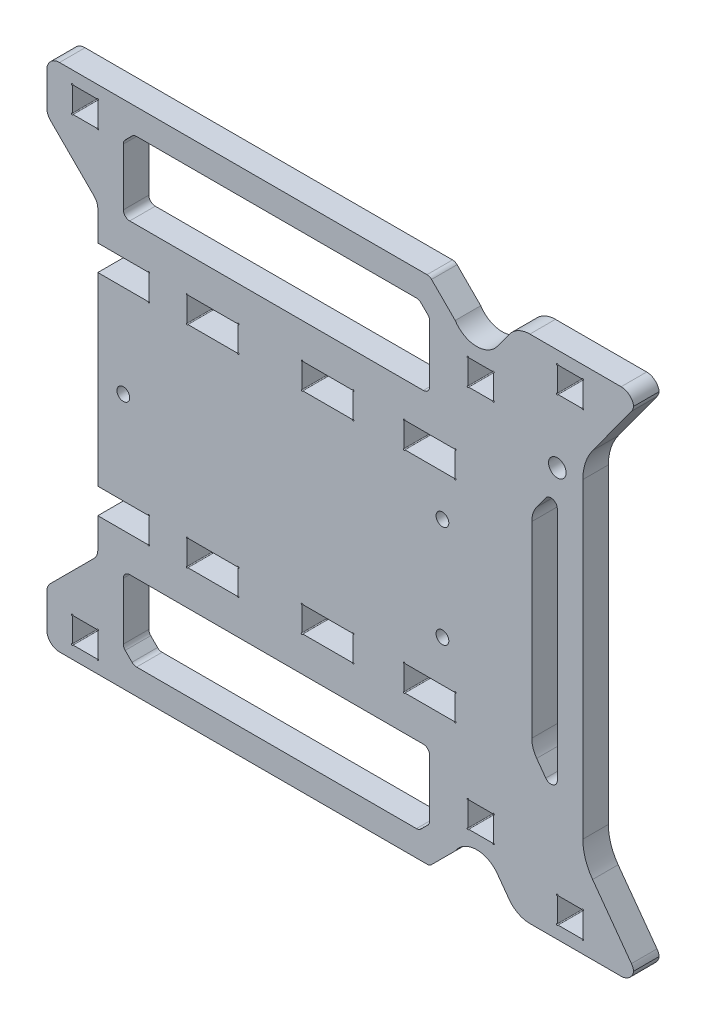
SolidWorks part; units mm, degrees
ref_plane "Front Plane" through (0, 0, 0) normal (0, 0, 1) x (1, 0, 0)
ref_plane "Top Plane" through (0, 0, 0) normal (0, 1, 0) x (1, 0, 0)
ref_plane "Right Plane" through (0, 0, 0) normal (1, 0, 0) x (0, 0, -1)
sketch "Sketch1" plane through (0, 0, 0) normal (0, 0, 1) x (1, 0, 0)
  line L0 (83.672, 0) -> (-43.8164, 0) construction
  line L1 (10.525, 38.1) -> (10.525, -38.1) construction
  line L2 (-27.575, 38.1) -> (48.625, 38.1)
  line L3 (99.425, -63.5) -> (99.425, -60.325)
  line L4 (99.425, -60.325) -> (74.025, -25.4)
  line L5 (-27.575, -63.5) -> (48.625, -63.5)
  line L6 (-27.575, 38.1) -> (-27.575, 54.5197)
  line L7 (48.625, 38.1) -> (48.625, 54.5197)
  line L8 (-24.9447, 57.15) -> (45.9947, 57.15)
  line L9 (-27.575, 63.5) -> (48.625, 63.5)
  line L10 (-33.925, 57.15) -> (-33.925, -57.15)
  line L11 (-27.575, 63.5) -> (-33.925, 57.15)
  line L12 (-24.9447, 57.15) -> (-27.575, 54.5197)
  line L13 (99.425, 63.5) -> (99.425, 60.325)
  line L14 (-23.0849, 59.0099) -> (-29.4349, 52.6599) construction
  line L15 (99.425, 60.325) -> (74.025, 25.4)
  line L16 (74.025, 25.4) -> (74.025, -25.4)
  line L17 (48.625, -38.1) -> (48.625, -54.5197)
  line L18 (-27.575, -38.1) -> (48.625, -38.1)
  line L19 (-24.9447, -57.15) -> (45.9947, -57.15)
  line L20 (-24.9447, -57.15) -> (-27.575, -54.5197)
  line L21 (-27.575, -38.1) -> (-27.575, -54.5197)
  line L22 (-27.575, -63.5) -> (-33.925, -57.15)
  line L23 (48.625, -63.5) -> (54.975, -57.15)
  line L24 (48.625, 63.5) -> (54.975, 57.15)
  line L25 (70.3271, -63.5) -> (99.425, -63.5)
  line L26 (45.9947, 57.15) -> (48.625, 54.5197)
  line L27 (45.9947, -57.15) -> (48.625, -54.5197)
  line L28 (70.3271, 63.5) -> (65.7089, 57.15)
  line L29 (70.3271, 63.5) -> (99.425, 63.5)
  line L30 (78.8831, 75.2646) -> (53.4831, 40.3396) construction
  line L31 (54.975, -42.3909) -> (54.975, -57.15)
  line L32 (70.3271, -63.5) -> (65.7089, -57.15)
  line L34 (48.625, -63.5) -> (54.975, -57.15)
  line L35 (65.7089, 57.15) -> (54.975, 42.3909)
  line L36 (54.975, 42.3909) -> (54.975, 57.15)
  line L37 (65.7089, -57.15) -> (54.975, -42.3909)
  point P7 (-27.575, 0)
  point P21 (74.025, 0)
  point P22 (-33.925, 0)
  dimension "D1" = 25.4
  dimension "D2" = 76.2
  dimension "D3" = 127
  dimension "D4" = 6.35
  dimension "D7" = 3.175
  dimension "D8" = 25.4
  dimension "D9" = 25.4
  dimension "D6" = 6.35
extrude "Boss-Extrude1" add sketch "Sketch1" along normal blind 6.35 contours L23 L32 L25 L3 L4 L16 L15 L13 L29 L28 L24 L9 L11 L10 L22 L5 L8 L26 L7 L2 L6 L12 L27 L19 L20 L21 L18 L17 region at (27.1557, 0, 0)
fillet "Fillet1" radius 6.35 4 edges at (70.3271, 63.5, 3.175) (70.3271, -63.5, 3.175) (54.975, -42.3909, 3.175) (54.975, 42.3909, 3.175)
fillet "Fillet3" radius 3.175 4 edges at (99.425, 63.5, 3.175) (99.425, 60.325, 3.175) (99.425, -60.325, 3.175) (99.425, -63.5, 3.175)
fillet "Fillet4" radius 6.35 2 edges at (74.025, -25.4, 3.175) (74.025, 25.4, 3.175)
fillet "Fillet7" radius 1.5875 4 edges at (-27.575, -38.1, 3.175) (48.625, -38.1, 3.175) (48.625, 38.1, 3.175) (-27.575, 38.1, 3.175)
fillet "Fillet8" radius 1.5875 2 edges at (48.625, -63.5, 3.175) (48.625, 63.5, 3.175)
fillet "Fillet9" radius 1.5875 8 edges at (-27.575, 54.5197, 3.175) (-24.9447, 57.15, 3.175) (-27.575, -54.5197, 3.175) (-24.9447, -57.15, 3.175) (45.9947, -57.15, 3.175) (48.625, -54.5197, 3.175) (48.625, 54.5197, 3.175) (45.9947, 57.15, 3.175)
sketch "Sketch2" plane through (0, 0, 6.35) normal (0, 0, 1) x (1, 0, 0)
  line L0 (-33.925, 0) -> (74.025, 0) construction
  line L1 (-33.925, 57.15) -> (-33.925, -57.15) construction
  line L2 (74.025, 23.3351) -> (74.025, -23.3351) construction
  line L3 (48.625, 39.6875) -> (48.625, 53.8622) construction
  line L4 (58.3484, 50.8) -> (64.3016, 50.8)
  line L5 (58.15, 50.6016) -> (58.15, 44.6484)
  line L6 (58.3484, 44.45) -> (64.3016, 44.45)
  line L7 (64.5, 50.6016) -> (64.5, 44.6484)
  line L8 (64.5, -50.6016) -> (64.5, -44.6484)
  line L9 (58.3484, -50.8) -> (64.3016, -50.8)
  line L10 (58.15, -50.6016) -> (58.15, -44.6484)
  line L11 (58.3484, -44.45) -> (64.3016, -44.45)
  arc A0 (58.3484, 50.8) -> (58.15, 50.6016) centre (58.15, 50.8) ccw
  arc A1 (64.5, 50.6016) -> (64.3016, 50.8) centre (64.5, 50.8) ccw
  arc A2 (64.3016, 44.45) -> (64.5, 44.6484) centre (64.5, 44.45) ccw
  arc A3 (58.15, 44.6484) -> (58.3484, 44.45) centre (58.15, 44.45) ccw
  arc A4 (64.3016, -44.45) -> (64.5, -44.6484) centre (64.5, -44.45) cw
  arc A5 (64.5, -50.6016) -> (64.3016, -50.8) centre (64.5, -50.8) cw
  arc A6 (58.3484, -50.8) -> (58.15, -50.6016) centre (58.15, -50.8) cw
  arc A7 (58.15, -44.6484) -> (58.3484, -44.45) centre (58.15, -44.45) cw
  point P10 (48.625, 46.7748)
  dimension "D5" = 0.3969
  dimension "D6" = 0.3969
  dimension "D7" = 0.3969
  dimension "D8" = 0.3969
  dimension "D1" = 6.35
  dimension "D2" = 6.35
  dimension "D3" = 50.8
  dimension "D4" = 9.525
extrude "Cut-Extrude1" cut sketch "Sketch2" against normal through all
sketch "Sketch5" plane through (0, 0, 6.35) normal (0, 0, 1) x (1, 0, 0)
  line L0 (-33.925, 29.3675) -> (74.025, 29.3675) construction
  line L1 (-33.925, 57.15) -> (-33.925, -57.15) construction
  line L2 (74.025, 23.3351) -> (74.025, -23.3351) construction
  line L3 (-25.9875, 38.1) -> (47.0375, 38.1) construction
  line L4 (-33.925, 23.0175) -> (74.025, 23.0175) construction
  line L5 (-33.925, 0) -> (74.025, 0) construction
  line L6 (-11.5016, 29.3675) -> (0.8016, 29.3675)
  line L7 (-11.7, 29.169) -> (-11.7, 23.2159)
  line L8 (-11.5016, 23.0175) -> (0.8016, 23.0175)
  line L9 (1, 29.169) -> (1, 23.2159)
  line L10 (42.4734, 29.3675) -> (54.7766, 29.3675)
  line L11 (42.275, 29.169) -> (42.275, 23.2159)
  line L12 (42.4734, 23.0175) -> (54.7766, 23.0175)
  line L13 (54.975, 29.169) -> (54.975, 23.2159)
  line L14 (29.3766, 29.3675) -> (17.0734, 29.3675)
  line L15 (29.575, 29.169) -> (29.575, 23.2159)
  line L16 (29.3766, 23.0175) -> (17.0734, 23.0175)
  line L17 (16.875, 29.169) -> (16.875, 23.2159)
  line L18 (-21.4234, 29.3675) -> (-33.925, 29.3675)
  line L19 (-21.225, 29.169) -> (-21.225, 23.2159)
  line L20 (-21.4234, 23.0175) -> (-33.925, 23.0175)
  line L21 (-33.925, 29.3675) -> (-33.925, 23.0175)
  line L22 (-33.925, -29.3675) -> (-33.925, -23.0175)
  line L23 (-21.4234, -23.0175) -> (-33.925, -23.0175)
  line L24 (-21.225, -29.169) -> (-21.225, -23.2159)
  line L25 (-21.4234, -29.3675) -> (-33.925, -29.3675)
  line L26 (16.875, -29.169) -> (16.875, -23.2159)
  line L27 (29.3766, -23.0175) -> (17.0734, -23.0175)
  line L28 (29.575, -29.169) -> (29.575, -23.2159)
  line L29 (29.3766, -29.3675) -> (17.0734, -29.3675)
  line L30 (54.975, -29.169) -> (54.975, -23.2159)
  line L31 (42.4734, -23.0175) -> (54.7766, -23.0175)
  line L32 (42.275, -29.169) -> (42.275, -23.2159)
  line L33 (42.4734, -29.3675) -> (54.7766, -29.3675)
  line L34 (1, -29.169) -> (1, -23.2159)
  line L35 (-11.5016, -23.0175) -> (0.8016, -23.0175)
  line L36 (-11.7, -29.169) -> (-11.7, -23.2159)
  line L37 (-11.5016, -29.3675) -> (0.8016, -29.3675)
  line L38 (-33.925, 26.1925) -> (54.975, 26.1925) construction
  arc A0 (-21.225, 29.169) -> (-21.4234, 29.3675) centre (-21.225, 29.3675) ccw
  arc A1 (-11.5016, 29.3675) -> (-11.7, 29.169) centre (-11.7, 29.3675) ccw
  arc A2 (1, 29.169) -> (0.8016, 29.3675) centre (1, 29.3675) ccw
  arc A3 (29.575, 29.169) -> (29.3766, 29.3675) centre (29.575, 29.3675) ccw
  arc A4 (17.0734, 29.3675) -> (16.875, 29.169) centre (16.875, 29.3675) ccw
  arc A5 (54.975, 29.169) -> (54.7766, 29.3675) centre (54.975, 29.3675) ccw
  arc A6 (42.4734, 29.3675) -> (42.275, 29.169) centre (42.275, 29.3675) ccw
  arc A7 (17.0734, 23.0175) -> (16.875, 23.2159) centre (16.875, 23.0175) cw
  arc A8 (29.575, 23.2159) -> (29.3766, 23.0175) centre (29.575, 23.0175) cw
  arc A9 (42.4734, 23.0175) -> (42.275, 23.2159) centre (42.275, 23.0175) cw
  arc A10 (54.975, 23.2159) -> (54.7766, 23.0175) centre (54.975, 23.0175) cw
  arc A11 (1, 23.2159) -> (0.8016, 23.0175) centre (1, 23.0175) cw
  arc A12 (-11.5016, 23.0175) -> (-11.7, 23.2159) centre (-11.7, 23.0175) cw
  arc A13 (-21.225, 23.2159) -> (-21.4234, 23.0175) centre (-21.225, 23.0175) cw
  arc A14 (-21.225, -23.2159) -> (-21.4234, -23.0175) centre (-21.225, -23.0175) ccw
  arc A15 (-11.5016, -23.0175) -> (-11.7, -23.2159) centre (-11.7, -23.0175) ccw
  arc A16 (1, -23.2159) -> (0.8016, -23.0175) centre (1, -23.0175) ccw
  arc A17 (54.975, -23.2159) -> (54.7766, -23.0175) centre (54.975, -23.0175) ccw
  arc A18 (42.4734, -23.0175) -> (42.275, -23.2159) centre (42.275, -23.0175) ccw
  arc A19 (29.575, -23.2159) -> (29.3766, -23.0175) centre (29.575, -23.0175) ccw
  arc A20 (17.0734, -23.0175) -> (16.875, -23.2159) centre (16.875, -23.0175) ccw
  arc A21 (42.4734, -29.3675) -> (42.275, -29.169) centre (42.275, -29.3675) cw
  arc A22 (54.975, -29.169) -> (54.7766, -29.3675) centre (54.975, -29.3675) cw
  arc A23 (17.0734, -29.3675) -> (16.875, -29.169) centre (16.875, -29.3675) cw
  arc A24 (29.575, -29.169) -> (29.3766, -29.3675) centre (29.575, -29.3675) cw
  arc A25 (1, -29.169) -> (0.8016, -29.3675) centre (1, -29.3675) cw
  arc A26 (-11.5016, -29.3675) -> (-11.7, -29.169) centre (-11.7, -29.3675) cw
  arc A27 (-21.225, -29.169) -> (-21.4234, -29.3675) centre (-21.225, -29.3675) cw
  dimension "D11" = 0.3969
  dimension "D12" = 0.3969
  dimension "D13" = 0.3969
  dimension "D14" = 0.3969
  dimension "D15" = 0.3969
  dimension "D16" = 0.3969
  dimension "D17" = 0.3969
  dimension "D1" = 8.7325
  dimension "D3" = 12.7
  dimension "D4" = 12.7
  dimension "D5" = 41.275
  dimension "D6" = 34.925
  dimension "D7" = 12.7
  dimension "D8" = 12.7
  dimension "D9" = 50.8
  dimension "D10" = 0
  dimension "D2" = 6.35
extrude "Cut-Extrude4" cut sketch "Sketch5" against normal through all
sketch "Sketch6" plane through (0, 0, 6.35) normal (0, 0, 1) x (1, 0, 0)
  line L0 (80.375, 34.1312) -> (80.375, -34.1312)
  line L1 (98.8177, 59.49) -> (75.2395, 27.07) construction
  line L2 (98.8177, -59.49) -> (75.2395, -27.07) construction
  line L3 (74.025, 23.3351) -> (74.025, -23.3351) construction
  line L4 (86.725, 34.1312) -> (86.725, -34.1312)
  line L5 (86.725, 34.1312) -> (86.725, 42.8625)
  line L6 (86.725, 42.8625) -> (80.375, 34.1312)
  line L7 (86.725, -34.1312) -> (86.725, -42.8625)
  line L8 (86.725, -42.8625) -> (80.375, -34.1312)
  dimension "D1" = 6.35
  dimension "D2" = 6.35
extrude "Boss-Extrude2" add sketch "Sketch6" against normal blind 6.35
fillet "Fillet10" radius 1.5875 2 edges at (80.375, -34.1312, 3.175) (80.375, 34.1312, 3.175)
fillet "Fillet11" radius 12.7 2 edges at (86.725, 42.8625, 3.175) (86.725, -42.8625, 3.175)
hole_wizard "11/64 (0.17188) Diameter Hole1" positions "Sketch8" profile "Sketch7" hole size "11/64" standard "ANSI Inch" end condition through all
sketch "Sketch8" plane through (0, 0, 6.35) normal (0, 0, 1) x (1, 0, 0)
  line L1 (-33.925, -29.3675) -> (-33.925, -57.15) construction
  line L2 (73.5606, 63.5) -> (96.25, 63.5) construction
  point P0 (80.375, 38.1)
  dimension "D1" = 25.4
  dimension "D2" = 114.3
sketch "Sketch7" plane through (80.375, 38.1, 6.35) normal (1, 0, 0) x (0, -1, 0)
  line L0 (0, 0) -> (0, 6.35)
  line L1 (0, 6.35) -> (2.1829, 6.35)
  line L2 (2.1829, 6.35) -> (2.1829, 0)
  line L5 (2.1829, 0) -> (0, 0)
  line L11 (0, -6.35) -> (0, 107.95) construction
  dimension "Thru Hole Dia." = 4.3658
  dimension "Thru Hole Depth" = 6.35
sketch "Sketch10" plane through (0, 0, 6.35) normal (0, 0, 1) x (1, 0, 0)
  line L0 (51.8, 63.5) -> (51.8, -63.5) construction
  line L1 (-27.575, 63.5) -> (47.9674, 63.5) construction
  line L2 (-27.575, -63.5) -> (47.9674, -63.5) construction
  line L3 (23.225, 29.3675) -> (23.225, -29.3675) construction
  line L4 (29.3766, 29.3675) -> (17.0734, 29.3675) construction
  line L5 (17.0734, -29.3675) -> (29.3766, -29.3675) construction
  line L6 (-27.575, 63.5) -> (-27.575, -63.5) construction
  line L7 (-33.925, 0) -> (74.025, 0) construction
  line L8 (-33.925, 23.0175) -> (-33.925, -23.0175) construction
  line L9 (74.025, 23.3351) -> (74.025, -23.3351) construction
  circle A0 centre (51.8, 12.7) radius 1.5875
  circle A1 centre (51.8, -12.7) radius 1.5875
  circle A2 centre (-27.575, 0) radius 1.5875
  dimension "D3" = 3.175
  dimension "D5" = 79.375
  dimension "D1" = 28.575
  dimension "D2" = 79.375
  dimension "D4" = 12.7
extrude "Cut-Extrude6" cut sketch "Sketch10" against normal through all
sketch "Sketch11" plane through (0, 0, 6.35) normal (0, 0, 1) x (1, 0, 0)
  line L0 (-62.0481, -60.325) -> (124.8486, -60.325) construction
  line L1 (-27.575, -63.5) -> (47.9674, -63.5) construction
  line L2 (-27.575, -63.5) -> (-33.925, -57.15)
  line L3 (-33.925, -57.15) -> (-33.925, -50.8)
  line L4 (-33.925, -50.8) -> (-33.925, -38.1)
  line L5 (-46.625, -50.8) -> (-46.625, -63.5)
  line L6 (-46.625, -63.5) -> (-27.575, -63.5)
  line L7 (-46.625, -50.8) -> (-33.925, -38.1)
  line L8 (-33.925, -29.3675) -> (-33.925, -57.15) construction
  line L9 (-46.625, 63.5) -> (-27.575, 63.5)
  line L10 (-33.925, 0) -> (74.025, 0) construction
  line L11 (-46.625, 50.8) -> (-46.625, 63.5)
  line L12 (-33.925, 23.0175) -> (-33.925, -23.0175) construction
  line L13 (74.025, 23.3351) -> (74.025, -23.3351) construction
  line L14 (-46.625, 50.8) -> (-33.925, 38.1)
  line L15 (-33.925, 57.15) -> (-33.925, 50.8)
  line L16 (-27.575, 63.5) -> (-33.925, 57.15)
  line L17 (-33.925, 50.8) -> (-33.925, 38.1)
  point P2 (10.1962, -63.5)
  dimension "D1" = 3.175
  dimension "D2" = 12.7
  dimension "D3" = 12.7
extrude "Boss-Extrude4" add sketch "Sketch11" against normal blind 6.35
sketch "Sketch12" plane through (0, 0, 6.35) normal (0, 0, 1) x (1, 0, 0)
  line L0 (73.5606, -63.5) -> (96.25, -63.5) construction
  line L1 (86.5266, -60.325) -> (80.5734, -60.325)
  line L2 (86.725, -60.1266) -> (86.725, -54.1734)
  line L3 (86.5266, -53.975) -> (80.5734, -53.975)
  line L4 (80.375, -60.1266) -> (80.375, -54.1734)
  line L5 (-33.925, -29.3675) -> (-33.925, -38.1) construction
  line L6 (-33.925, 0) -> (74.025, 0) construction
  line L7 (86.725, 60.1266) -> (86.725, 54.1734)
  line L8 (86.5266, 60.325) -> (80.5734, 60.325)
  line L9 (80.375, 60.1266) -> (80.375, 54.1734)
  line L10 (86.5266, 53.975) -> (80.5734, 53.975)
  line L11 (83.55, -60.325) -> (-33.7266, -60.325) construction
  line L12 (-34.1234, -60.325) -> (-54.5439, -60.325) construction
  line L13 (-34.1234, -60.325) -> (-40.0766, -60.325)
  line L14 (-33.925, -60.1266) -> (-33.925, -54.1734)
  line L15 (-34.1234, -53.975) -> (-40.0766, -53.975)
  line L16 (-40.275, -60.1266) -> (-40.275, -54.1734)
  line L17 (-34.1234, 60.325) -> (-40.0766, 60.325)
  line L18 (-33.925, 60.1266) -> (-33.925, 54.1734)
  line L19 (-40.275, 60.1266) -> (-40.275, 54.1734)
  line L20 (-34.1234, 53.975) -> (-40.0766, 53.975)
  arc A0 (-40.275, 60.1266) -> (-40.0766, 60.325) centre (-40.275, 60.325) cw
  arc A1 (80.5734, -53.975) -> (80.375, -54.1734) centre (80.375, -53.975) ccw
  arc A2 (86.725, -54.1734) -> (86.5266, -53.975) centre (86.725, -53.975) ccw
  arc A3 (80.375, -60.1266) -> (80.5734, -60.325) centre (80.375, -60.325) ccw
  arc A4 (86.5266, -60.325) -> (86.725, -60.1266) centre (86.725, -60.325) ccw
  arc A5 (86.5266, 60.325) -> (86.725, 60.1266) centre (86.725, 60.325) cw
  arc A6 (80.375, 60.1266) -> (80.5734, 60.325) centre (80.375, 60.325) cw
  arc A7 (80.5734, 53.975) -> (80.375, 54.1734) centre (80.375, 53.975) cw
  arc A8 (86.725, 54.1734) -> (86.5266, 53.975) centre (86.725, 53.975) cw
  arc A9 (-40.0766, -53.975) -> (-40.275, -54.1734) centre (-40.275, -53.975) ccw
  arc A10 (-33.925, -54.1734) -> (-34.1234, -53.975) centre (-33.925, -53.975) ccw
  arc A11 (-34.1234, -60.325) -> (-33.925, -60.1266) centre (-33.925, -60.325) ccw
  arc A12 (-40.275, -60.1266) -> (-40.0766, -60.325) centre (-40.275, -60.325) ccw
  arc A13 (-34.1234, 60.325) -> (-33.925, 60.1266) centre (-33.925, 60.325) cw
  arc A14 (-33.925, 54.1734) -> (-34.1234, 53.975) centre (-33.925, 53.975) cw
  arc A15 (-40.0766, 53.975) -> (-40.275, 54.1734) centre (-40.275, 53.975) cw
  point P4 (84.9053, -63.5)
  dimension "D5" = 0.3969
  dimension "D6" = 0.3969
  dimension "D7" = 0.3969
  dimension "D8" = 0.3969
  dimension "D12" = 0.3969
  dimension "D13" = 0.3969
  dimension "D14" = 0.3969
  dimension "D15" = 0.3969
  dimension "D1" = 6.35
  dimension "D2" = 6.35
  dimension "D3" = 3.175
  dimension "D4" = 114.3
  dimension "D9" = 6.35
  dimension "D10" = 6.35
  dimension "D11" = 120.65
extrude "Cut-Extrude7" cut sketch "Sketch12" against normal blind 6.35
fillet "Fillet12" radius 3.175 6 edges at (-46.625, 63.5, 3.175) (-46.625, 50.8, 3.175) (-33.925, 38.1, 3.175) (-46.625, -63.5, 3.175) (-46.625, -50.8, 3.175) (-33.925, -38.1, 3.175)
